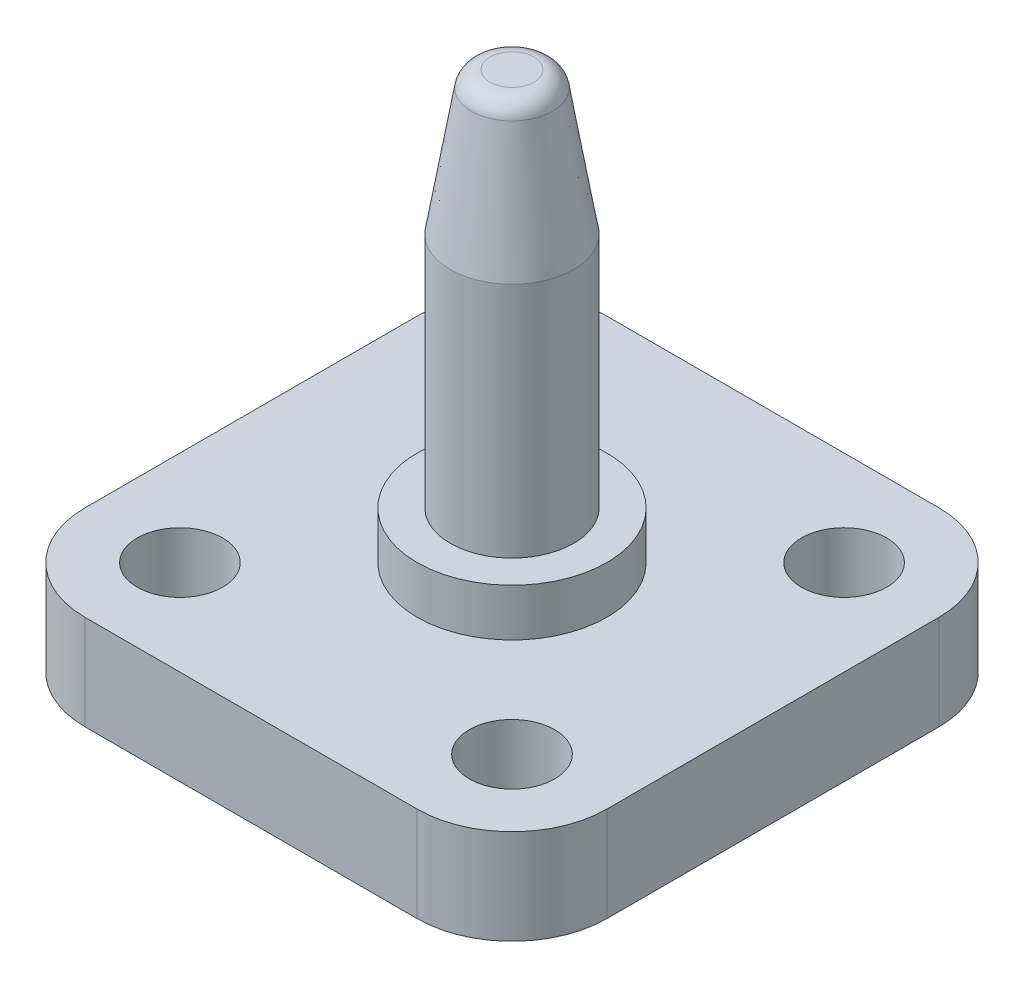
SolidWorks part; units mm, degrees
ref_plane "Front Plane" through (0, 0, 0) normal (0, 0, 1) x (1, 0, 0)
ref_plane "Top Plane" through (0, 0, 0) normal (0, 1, 0) x (1, 0, 0)
ref_plane "Right Plane" through (0, 0, 0) normal (1, 0, 0) x (0, 0, -1)
sketch "Sketch1" plane through (0, 0, 0) normal (0, 0, 1) x (1, 0, 0)
  line L0 (0, 22.5) -> (0, -22.5) construction
  line L1 (0, 22.5) -> (2.3057, 22.5)
  line L2 (4.2785, 20.8288) -> (6.5, 7.5)
  line L3 (6.5, 7.5) -> (6.5, -17.5)
  line L4 (6.5, -22.5) -> (0, -22.5)
  line L5 (0, 22.5) -> (0, -22.5)
  line L6 (6.5, -17.5) -> (10, -17.5)
  line L7 (10, -17.5) -> (10, -22.5)
  line L8 (10, -22.5) -> (6.5, -22.5)
  arc A0 (2.3057, 22.5) -> (4.2785, 20.8288) centre (2.3057, 20.5) cw
  point P4 (0, 0)
  point P10 (4, 22.5)
  dimension "D5" = 2
  dimension "D1" = 30
  dimension "D2" = 15
  dimension "D3" = 13
  dimension "D4" = 4
  dimension "D6" = 10
  dimension "D7" = 5
revolve "Revolve1" add sketch "Sketch1" angle 360 about L0
sketch "Sketch2" plane through (0, -22.5, 0) normal (0, -1, 0) x (1, 0, 0)
  line L0 (27.5, 27.5) -> (-27.5, -27.5) construction
  line L1 (17.5, 27.5) -> (-17.5, 27.5)
  line L2 (27.5, 17.5) -> (27.5, -17.5)
  line L3 (17.5, -27.5) -> (-17.5, -27.5)
  line L4 (-27.5, 17.5) -> (-27.5, -17.5)
  arc A0 (-17.5, 27.5) -> (-27.5, 17.5) centre (-17.5, 17.5) ccw
  arc A1 (-17.5, -27.5) -> (-27.5, -17.5) centre (-17.5, -17.5) cw
  arc A2 (27.5, -17.5) -> (17.5, -27.5) centre (17.5, -17.5) cw
  arc A3 (17.5, 27.5) -> (27.5, 17.5) centre (17.5, 17.5) cw
  dimension "D2" = 10
  dimension "D1" = 55
extrude "Boss-Extrude1" add sketch "Sketch2" along normal blind 10
sketch "Sketch3" plane through (0, -22.5, 0) normal (0, 1, 0) x (1, 0, 0)
  circle A0 centre (-17.5, 17.5) radius 4.5
  dimension "D1" = 9
extrude "Cut-Extrude1" cut sketch "Sketch3" against normal through all
mirror "Mirror1" about plane through (0, 0, 0) normal (0, 0, 1) of "Cut-Extrude1" second plane through (0, 0, 0) second plane normal (1, 0, 0)
